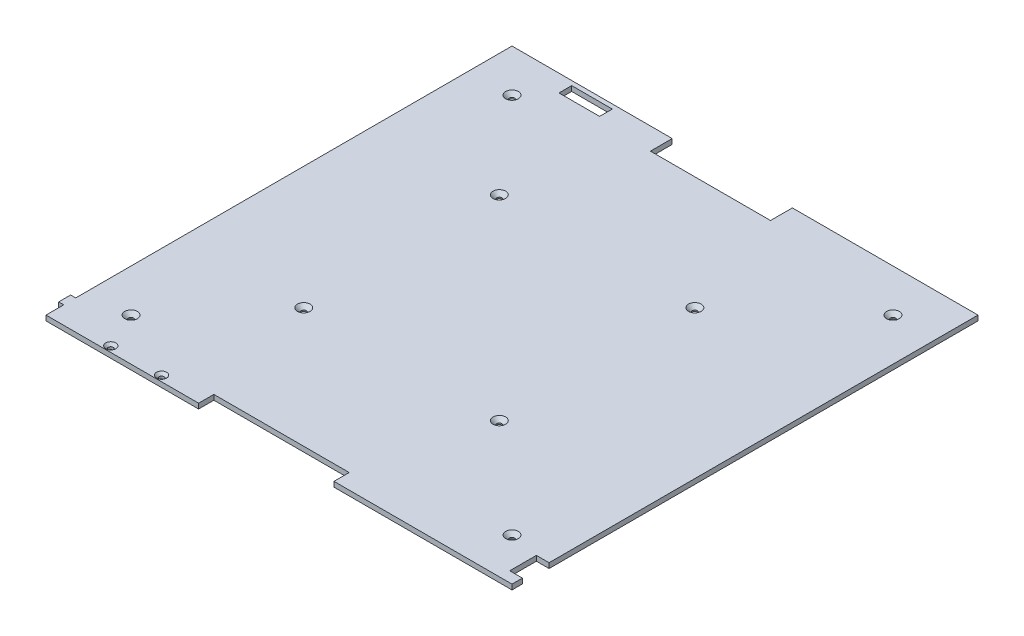
SolidWorks part; units mm, degrees
ref_plane "Front Plane" through (0, 0, 0) normal (0, 0, 1) x (1, 0, 0)
ref_plane "Top Plane" through (0, 0, 0) normal (0, 1, 0) x (1, 0, 0)
ref_plane "Right Plane" through (0, 0, 0) normal (1, 0, 0) x (0, 0, -1)
sketch "Sketch1" plane through (0, 0, 0) normal (0, 1, 0) x (1, 0, 0)
  line L0 (-92, 92) -> (-92, -79.8) construction
  line L1 (-28.4, 92) -> (-92, 92) construction
  line L2 (-28.4, 83.4) -> (-28.4, 92) construction
  line L3 (18.4, 83.4) -> (-28.4, 83.4) construction
  line L4 (18.4, 92) -> (18.4, 83.4) construction
  line L5 (92, 92) -> (18.4, 92) construction
  line L6 (92, -77.4) -> (92, 92) construction
  line L7 (87, -77.4) -> (92, -77.4) construction
  line L8 (87, -87.4) -> (87, -77.4) construction
  line L9 (92, -87.4) -> (87, -87.4) construction
  line L10 (92, -92) -> (92, -87.4) construction
  line L11 (21.4, -92) -> (92, -92) construction
  line L12 (21.4, -86) -> (21.4, -92) construction
  line L13 (-31.4, -86) -> (21.4, -86) construction
  line L14 (-31.4, -92) -> (-31.4, -86) construction
  line L15 (-92, -92) -> (-31.4, -92) construction
  line L16 (-92, -85) -> (-92, -92) construction
  line L17 (-94, -85) -> (-92, -85) construction
  line L18 (-94, -79.8) -> (-94, -85) construction
  line L19 (-92, -79.8) -> (-94, -79.8) construction
  line L20 (-91.75, 91.75) -> (-91.75, -80.05)
  line L21 (-91.75, -80.05) -> (-93.75, -80.05)
  line L22 (-93.75, -80.05) -> (-93.75, -84.75)
  line L23 (-93.75, -84.75) -> (-91.75, -84.75)
  line L24 (-91.75, -84.75) -> (-91.75, -91.75)
  line L25 (-91.75, -91.75) -> (-31.65, -91.75)
  line L26 (-31.65, -91.75) -> (-31.65, -85.75)
  line L27 (-31.65, -85.75) -> (21.65, -85.75)
  line L28 (21.65, -85.75) -> (21.65, -91.75)
  line L29 (21.65, -91.75) -> (91.75, -91.75)
  line L30 (91.75, -91.75) -> (91.75, -87.65)
  line L31 (91.75, -87.65) -> (86.75, -87.65)
  line L32 (86.75, -87.65) -> (86.75, -77.15)
  line L33 (86.75, -77.15) -> (91.75, -77.15)
  line L34 (91.75, -77.15) -> (91.75, 91.75)
  line L35 (91.75, 91.75) -> (18.65, 91.75)
  line L36 (18.65, 91.75) -> (18.65, 83.15)
  line L37 (18.65, 83.15) -> (-28.65, 83.15)
  line L38 (-28.65, 83.15) -> (-28.65, 91.75)
  line L39 (-28.65, 91.75) -> (-91.75, 91.75)
  dimension "D1" = 184
  dimension "D2" = 184
  dimension "D3" = 8.6
  dimension "D4" = 63.6
  dimension "D5" = 46.8
  dimension "D6" = 2
  dimension "D7" = 7
  dimension "D8" = 5.2
  dimension "D9" = 4.6
  dimension "D10" = 10
  dimension "D11" = 70.6
  dimension "D12" = 52.8
  dimension "D13" = 5
  dimension "D14" = 6
  dimension "D15" = 92
  dimension "D16" = 92
  dimension "D17" = 0.25
extrude "Boss-Extrude1" add sketch "Sketch1" along normal blind 2
sketch "Sketch2" plane through (0, 0, 0) normal (0, -1, 0) x (1, 0, 0)
  circle A0 centre (75, -75) radius 1
  circle A1 centre (-75, -75) radius 1
  circle A2 centre (-75, 75) radius 1
  circle A3 centre (75, 75) radius 1
  circle A4 centre (33.5, -38.5) radius 1
  circle A5 centre (33.5, 38.5) radius 1
  circle A6 centre (-43.5, -38.5) radius 1
  circle A7 centre (-43.5, 38.5) radius 1
  dimension "D1" = 2
  dimension "D2" = 2
  dimension "D3" = 2
  dimension "D4" = 2
  dimension "D5" = 2
  dimension "D6" = 2
  dimension "D7" = 2
  dimension "D8" = 2
extrude "Cut-Extrude1" cut sketch "Sketch2" against normal through all
chamfer "Chamfer1" distance 1.5 angle 45 8 edges at (75, 2, -76) (33.5, 2, -39.5) (75, 2, 74) (33.5, 2, 37.5) (-43.5, 2, 37.5) (-43.5, 2, -39.5) (-75, 2, -76) (-75, 2, 74)
sketch "Sketch3" plane through (0, 0, 0) normal (0, -1, 0) x (1, 0, 0)
  line L1 (-50.5, -90) -> (-66.5, -90)
  line L2 (-50.5, -90) -> (-50.5, -85)
  line L3 (-50.5, -85) -> (-66.5, -85)
  line L4 (-66.5, -90) -> (-66.5, -85)
extrude "Cut-Extrude2" cut sketch "Sketch3" against normal through all
sketch "Sketch4" plane through (0, 0, 0) normal (0, -1, 0) x (1, 0, 0)
  line L0 (-28.65, -91.75) -> (-91.75, -91.75) construction
  line L1 (-47.4296, -19.75) -> (-39.8007, -19.75)
  line L2 (-47.4296, -19.75) -> (-47.4296, 20.25)
  line L3 (-47.4296, 20.25) -> (-39.8007, 20.25)
  line L4 (-39.8007, -19.75) -> (-39.8007, 20.25)
  line L5 (-91.75, -91.75) -> (-91.75, 80.05) construction
  dimension "D1" = 72
  dimension "D2" = 7.6289
  dimension "D3" = 44.3204
  dimension "D4" = 40
extrude "Cut-Extrude3" cut sketch "Sketch4" against normal blind 1.4
sketch "Sketch5" plane through (0, 0, 0) normal (0, -1, 0) x (1, 0, 0)
  circle A0 centre (-48.5, 89.5) radius 1
  circle A1 centre (-68.5, 89.5) radius 1
  dimension "D1" = 2
  dimension "D2" = 2
extrude "Cut-Extrude4" cut sketch "Sketch5" against normal through all
chamfer "Chamfer2" distance 1 angle 45 2 edges at (-48.5, 2, 88.5) (-68.5, 2, 88.5)
